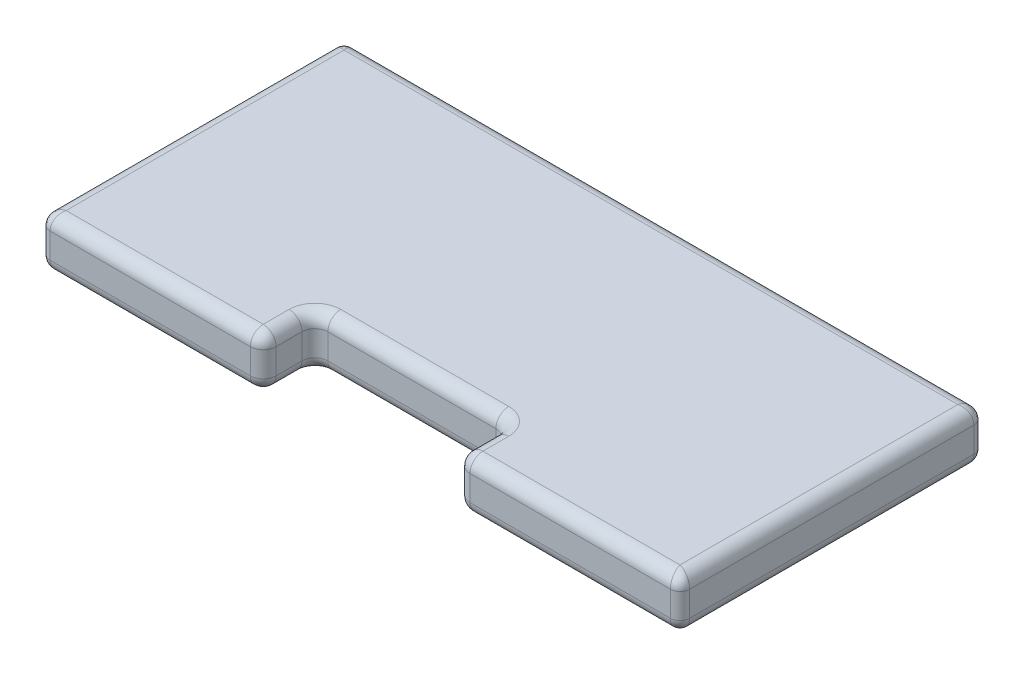
SolidWorks part; units mm, degrees
material "Nylon 6/10"
ref_plane "Piano frontale" through (0, 0, 0) normal (0, 0, 1) x (1, 0, 0)
ref_plane "Piano superiore" through (0, 0, 0) normal (0, 1, 0) x (1, 0, 0)
ref_plane "Piano destro" through (0, 0, 0) normal (1, 0, 0) x (0, 0, -1)
sketch "Schizzo1" plane through (0, 0, 0) normal (0, 1, 0) x (1, 0, 0)
  line L8 (-82.5958, -9.175) -> (-34.5958, -9.175)
  line L9 (-83.3458, 13.575) -> (-83.3458, -8.425)
  line L10 (-34.5958, 14.325) -> (-82.5958, 14.325)
  line L11 (-33.8458, -8.425) -> (-33.8458, 13.575)
  line L12 (-82.5958, -9.175) -> (-34.5958, -9.175)
  line L13 (-83.3458, 13.575) -> (-83.3458, -8.425)
  line L14 (-34.5958, 14.325) -> (-82.5958, 14.325)
  line L15 (-33.8458, -8.425) -> (-33.8458, 13.575)
  arc A8 (-34.5958, -9.175) -> (-33.8458, -8.425) centre (-34.5958, -8.425) ccw
  arc A9 (-83.3458, -8.425) -> (-82.5958, -9.175) centre (-82.5958, -8.425) ccw
  arc A10 (-82.5958, 14.325) -> (-83.3458, 13.575) centre (-82.5958, 13.575) ccw
  arc A11 (-33.8458, 13.575) -> (-34.5958, 14.325) centre (-34.5958, 13.575) ccw
  arc A12 (-34.5958, -9.175) -> (-33.8458, -8.425) centre (-34.5958, -8.425) ccw
  arc A13 (-83.3458, -8.425) -> (-82.5958, -9.175) centre (-82.5958, -8.425) ccw
  arc A14 (-82.5958, 14.325) -> (-83.3458, 13.575) centre (-82.5958, 13.575) ccw
  arc A15 (-33.8458, 13.575) -> (-34.5958, 14.325) centre (-34.5958, 13.575) ccw
  dimension "D1" = 0.25
extrude "Estrusione-Estrusione1" add sketch "Schizzo1" against normal up to surface (3.95 mm away)
sketch "Schizzo2" plane through (0, -3.95, 0) normal (0, -1, 0) x (1, 0, 0)
  line L0 (-58.5958, 5.175) -> (-58.5958, 9.175) construction
  line L1 (-66.0958, 9.175) -> (-51.0958, 9.175)
  line L2 (-66.0958, 9.175) -> (-66.0958, 5.175)
  line L3 (-66.0958, 5.175) -> (-51.0958, 5.175)
  line L4 (-51.0958, 9.175) -> (-51.0958, 5.175)
  line L5 (-66.0958, 9.175) -> (-51.0958, 5.175) construction
  line L6 (-66.0958, 5.175) -> (-51.0958, 9.175) construction
  line L7 (-83.3458, 8.425) -> (-83.3458, -13.575) construction
  line L8 (-33.8458, -13.575) -> (-33.8458, 8.425) construction
  line L9 (-34.5958, 9.175) -> (-82.5958, 9.175) construction
  point P0 (-58.5958, 7.175)
  dimension "D1" = 15
  dimension "D2" = 4
extrude "Taglio-Estrusione1" cut sketch "Schizzo2" against normal through all
fillet "Raccordo1" radius 1 28 edges at (-34.0655, -3.95, 8.9553) (-33.8458, -3.95, -2.575) (-34.0655, -3.95, -14.1053) (-58.5958, -3.95, -14.325) (-83.1261, -3.95, -14.1053) (-83.3458, -3.95, -2.575) (-83.1261, -3.95, 8.9553) (-74.3458, -3.95, 9.175) (-66.0958, -3.95, 7.175) (-58.5958, -3.95, 5.175) (-51.0958, -3.95, 7.175) (-42.8458, -3.95, 9.175) (-58.5958, 0, 5.175) (-66.0958, 0, 7.175) (-74.3458, 0, 9.175) (-83.1261, 0, 8.9553) (-83.3458, 0, -2.575) (-83.1261, 0, -14.1053) (-58.5958, 0, -14.325) (-34.0655, 0, -14.1053) (-33.8458, 0, -2.575) (-34.0655, 0, 8.9553) (-42.8458, 0, 9.175) (-51.0958, 0, 7.175) (-51.0958, -1.975, 9.175) (-51.0958, -1.975, 5.175) (-66.0958, -1.975, 5.175) (-66.0958, -1.975, 9.175)
sketch "Schizzo3" plane through (0, -3.95, 0) normal (0, 1, 0) x (1, 0, 0)
  line L0 (-82.3458, 4.575) -> (-34.8458, 4.575) construction
  line L1 (-58.5958, 13.325) -> (-58.5958, -4.175) construction
  line L2 (-34.8458, 13.325) -> (-82.3458, 13.325) construction
  line L3 (-65.0958, -4.175) -> (-52.0958, -4.175) construction
  line L4 (-82.3458, 13.325) -> (-82.3458, -8.175) construction
  text T0 "STIG" font "Racing Sans One" height 5
  point P12 (-58.5958, 4.575)
extrude "Estrusione-Estrusione2" add sketch "Schizzo3" against normal blind 2
